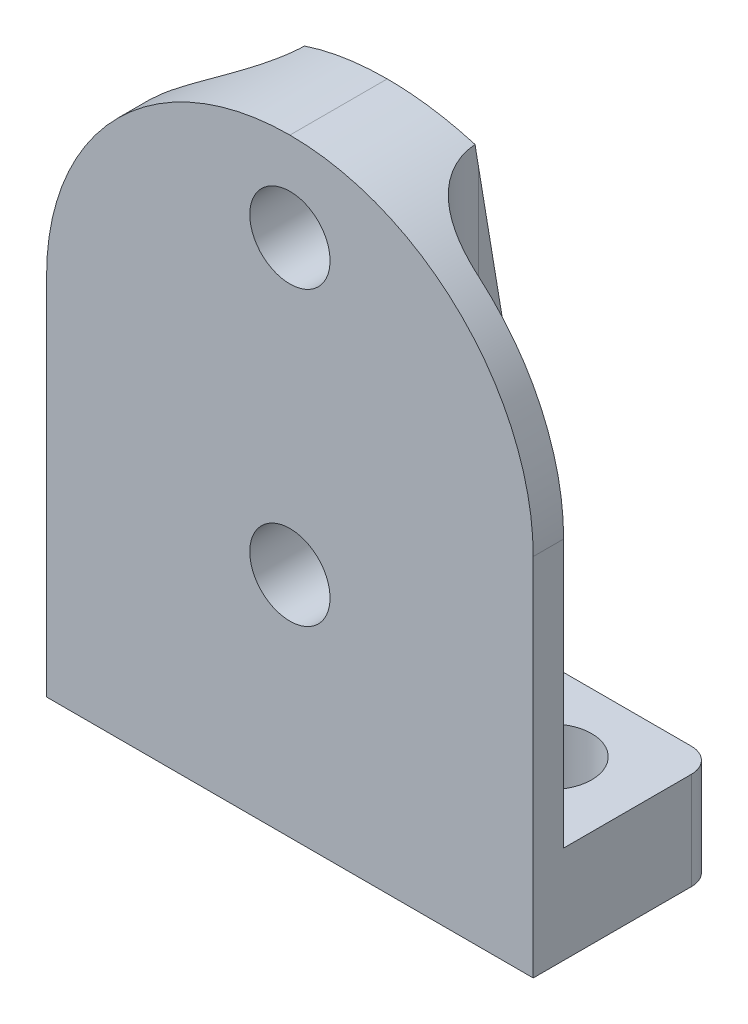
SolidWorks part; units mm, degrees
material "PETG"
ref_plane "Спереди" through (0, 0, 0) normal (0, 0, 1) x (1, 0, 0)
ref_plane "Сверху" through (0, 0, 0) normal (0, 1, 0) x (1, 0, 0)
ref_plane "Справа" through (0, 0, 0) normal (1, 0, 0) x (0, 0, -1)
sketch "Эскиз1" plane through (0, 0, 0) normal (1, 0, 0) x (0, 0, -1)
  line L0 (0, 0) -> (-9340.5259, 0) construction
  line L1 (0, 0) -> (0, 9340.5259) construction
  line L2 (0, 0) -> (7.5, 0)
  line L4 (0, 25) -> (0, 0)
  line L5 (0, 25) -> (4, 25)
  line L6 (4, 25) -> (7.5, 4)
  line L7 (7.5, 4) -> (7.5, 0)
  dimension "D1" = 7.5
  dimension "D2" = 25
  dimension "D3" = 4
extrude "Бобышка-Вытянуть1" add sketch "Эскиз1" along normal blind 20
ref_plane "Плоскость1" through (0, 0, -4) normal (0, 0, 1) x (1, 0, 0)
ref_plane "Плоскость2" through (0, 4, 0) normal (0, -1, 0) x (-1, 0, 0)
sketch "Эскиз2" plane through (0, 4, 0) normal (0, -1, 0) x (-1, 0, 0)
  line L0 (-20, 4.25) -> (0, 4.25) construction
  line L3 (-10, 7.5) -> (-10, 0) construction
  line L4 (-20, 7.5) -> (0, 7.5) construction
  line L5 (-20, 0) -> (0, 0) construction
  line L6 (-20, 0) -> (-20, 7.5) construction
  line L7 (0, 0) -> (0, 7.5) construction
  line L8 (-20, 3.75) -> (0, 3.75) construction
  circle A0 centre (-16.5, 4.25) radius 1.65
  circle A1 centre (-3.5, 4.25) radius 1.65
  dimension "D2" = 3.3
  dimension "D1" = 13
  dimension "D3" = 0.5
extrude "Вырез-Вытянуть1" cut sketch "Эскиз2" along normal up to surface (4 mm away) and the other way up to surface up to face at (10, 0, -3.75) other way up to face at (10, 14.5, -5.75)
sketch "Эскиз3" plane through (0, 4, 0) normal (0, -1, 0) x (-1, 0, 0)
  circle A0 centre (-16.5, 4.25) radius 3
  circle A1 centre (-3.5, 4.25) radius 3
  dimension "D1" = 6
extrude "Вырез-Вытянуть2" cut sketch "Эскиз3" against normal up to surface (1.5 mm away) up to face at (10, 16.9, -5.35)
sketch "Эскиз4" plane through (0, 0, -4) normal (0, 0, 1) x (1, 0, 0)
  line L0 (10, 3) -> (10, 50003) construction
  line L1 (20, 4) -> (0, 4) construction
  line L4 (13.5104, 25) -> (6.4896, 25) construction
  circle A0 centre (10, 21.35) radius 1.65
  circle A1 centre (10, 9.35) radius 1.65
  point P4 (10, 4)
  dimension "D1" = 3.3
  dimension "D3" = 2
  dimension "D2" = 12
extrude "Вырез-Вытянуть3" cut sketch "Эскиз4" along normal up to surface (4 mm away) and the other way up to surface up to face at (10, 12.5, 0) other way up to face at (10, 14.875, -5.6875)
sketch "Эскиз5" plane through (0, 0, -4) normal (0, 0, 1) x (1, 0, 0)
  circle A0 centre (10, 21.35) radius 3
  circle A1 centre (10, 9.35) radius 3
  circle A2 centre (10, 21.35) radius 5 construction
  circle A3 centre (10, 9.35) radius 5 construction
  dimension "D1" = 6
  dimension "D2" = 10
extrude "Вырез-Вытянуть7" cut sketch "Эскиз5" against normal up to surface (0.6083 mm away) up to face at (10, 23, -4.3333)
sketch "Эскиз6" plane through (0, 25, 0) normal (0, 1, 0) x (1, 0, 0)
  line L0 (0, 7.5) -> (0, 1.25)
  line L1 (6.5, 4.25) -> (3.5, 4.25)
  line L2 (3.5, 1.25) -> (0, 1.25)
  line L3 (6.5, 4.25) -> (6.5, 7.5)
  line L4 (20, 7.5) -> (0, 7.5) construction
  line L5 (6.5, 7.5) -> (0, 7.5)
  line L6 (0, 4) -> (0, 0) construction
  line L7 (10, 7.5) -> (10, 0) construction
  line L8 (20, 0) -> (0, 0) construction
  line L13 (3.5, 1.25) -> (3.5, 4.25)
  line L14 (13.5, 4.25) -> (16.5, 4.25)
  line L15 (16.5, 1.25) -> (16.5, 4.25)
  line L16 (16.5, 1.25) -> (20, 1.25)
  line L17 (20, 7.5) -> (20, 1.25)
  line L18 (13.5, 7.5) -> (20, 7.5)
  line L19 (13.5, 4.25) -> (13.5, 7.5)
  arc A0 (0.5104, 4) -> (6.4896, 4) centre (3.5, 4.25) ccw construction
  circle A1 centre (3.5, 4.25) radius 3 construction
extrude "Вырез-Вытянуть8" cut sketch "Эскиз6" against normal up to surface (21 mm away) up to face at (3.5, 4, -5.9)
fillet "Скругление1" radius 10 2 edges at (0, 25, -0.625) (20, 25, -0.625)
fillet "Скругление2" radius 1 2 edges at (0, 2, -7.5) (20, 2, -7.5)
